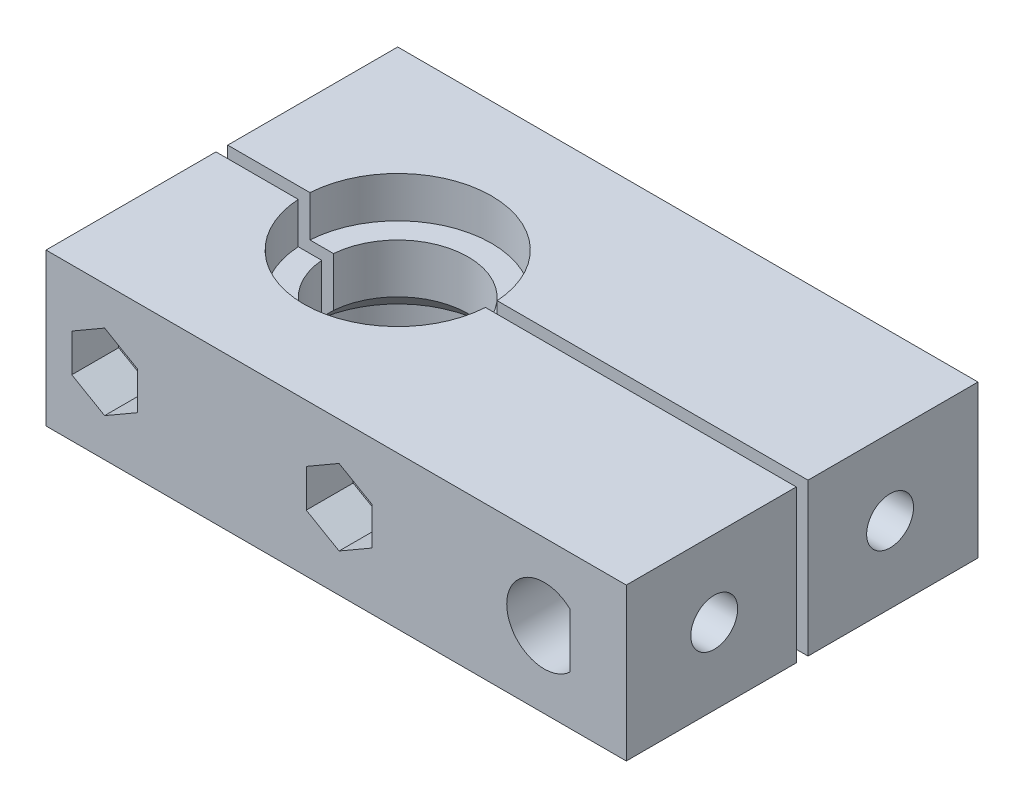
SolidWorks part; units mm, degrees
material "S235JR"
ref_plane "xy" through (0, 0, 0) normal (0, 0, 1) x (1, 0, 0)
ref_plane "xz" through (0, 0, 0) normal (0, 1, 0) x (1, 0, 0)
ref_plane "yz" through (0, 0, 0) normal (1, 0, 0) x (0, 0, -1)
ref_axis "x" through (-88.99, 0, 0) along (1, 0, 0)
ref_axis "y" through (0, 55, 0) along (0, -1, 0)
ref_axis "z" through (0, 0, -88.99) along (0, 0, 1)
sketch "Skizze1" plane through (0, 0, 0) normal (0, 0, 1) x (1, 0, 0)
  line L0 (2, 2.2361) -> (2, -2.2361) construction
  line L1 (-27.5, 6.5) -> (-27.5, -6.5) construction
  line L2 (-42.5, 6.5) -> (7, 6.5)
  line L3 (-42.5, 6.5) -> (-42.5, -6.5)
  line L4 (-42.5, -6.5) -> (7, -6.5)
  line L5 (7, 6.5) -> (7, -6.5)
  line L6 (-37.5, 0) -> (-17.5, 0) construction
  line L7 (2.2, 2.3238) -> (2.2, -2.3238)
  arc A0 (2, 2.2361) -> (2, -2.2361) centre (0, 0) ccw construction
  circle A1 centre (-17.5, 0) radius 1.7
  circle A2 centre (-37.5, 0) radius 1.7
  arc A3 (2.2, 2.3238) -> (2.2, -2.3238) centre (0, 0) ccw
  point P8 (7, 0)
  point P13 (-27.5, 0)
  dimension "D1" = 3
  dimension "D7" = 3.4
  dimension "D2" = 2
  dimension "D3" = 13
  dimension "D4" = 7
  dimension "D5" = 27.5
  dimension "D6" = 15
  dimension "D8" = 20
  dimension "D9" = 0.2
extrude "Aufsatz-Linear austragen1" add sketch "Skizze1" along normal blind 15
sketch "Skizze2" plane through (0, 0, 15) normal (0, 0, 1) x (1, 0, 0)
  line L0 (-35.5, 6.5) -> (-35.5, 3)
  line L1 (-35.5, 3) -> (-33.5, 3)
  line L2 (-33.5, 3) -> (-33.5, -3)
  line L3 (-33.5, -3) -> (-35.5, -3)
  line L4 (-35.5, -3) -> (-35.5, -6.5)
  line L5 (-35.5, -6.5) -> (-27.5, -6.5)
  line L6 (-27.5, -6.5) -> (-27.5, 6.5)
  line L7 (-27.5, 6.5) -> (-35.5, 6.5)
  point P13 (-33.5, 0)
  dimension "D1" = 6
  dimension "D2" = 6
  dimension "D3" = 8
revolve "Schnitt-Rotation1" cut sketch "Skizze2" angle 360 about L6
chamfer "Fase1" distance 1.8 angle 45 1 edges at (-27.5, -3, 9)
sketch "Skizze3" plane through (0, 0, 0) normal (0, 0, 1) x (1, 0, 0)
  line L1 (-14.7, -1.6166) -> (-14.7, 1.6166)
  line L2 (-14.7, 1.6166) -> (-17.5, 3.2332)
  line L3 (-17.5, 3.2332) -> (-20.3, 1.6166)
  line L4 (-20.3, 1.6166) -> (-20.3, -1.6166)
  line L5 (-20.3, -1.6166) -> (-17.5, -3.2332)
  line L6 (-17.5, -3.2332) -> (-14.7, -1.6166)
  line L7 (-37.5, -3.2332) -> (-34.7, -1.6166)
  line L8 (-34.7, -1.6166) -> (-34.7, 1.6166)
  line L9 (-34.7, 1.6166) -> (-37.5, 3.2332)
  line L10 (-37.5, 3.2332) -> (-40.3, 1.6166)
  line L11 (-40.3, 1.6166) -> (-40.3, -1.6166)
  line L12 (-40.3, -1.6166) -> (-37.5, -3.2332)
  circle A0 centre (-17.5, 0) radius 2.8 construction
  circle A1 centre (-37.5, 0) radius 2.8 construction
  dimension "D1" = 5.6
extrude "Schnitt-Linear austragen1" cut sketch "Skizze3" along normal blind 4
sketch "Skizze4" plane through (7, 0, 0) normal (1, 0, 0) x (0, 0, -1)
  line L0 (-15, -6.5) -> (0, 6.5) construction
  circle A0 centre (-7.5, 0) radius 2
  dimension "D1" = 4
extrude "Schnitt-Linear austragen2" cut sketch "Skizze4" against normal up to surface (4.8 mm away) up to face at (2.2, 0, 7.5)
mirror "Spiegeln1" about plane through (0, 0, 15) normal (0, 0, 1) of bodies 104
sketch "Skizze5" plane through (0, 0, 0) normal (0, 1, 0) x (1, 0, 0)
  line L0 (-27.5, -15) -> (-35.5, -15) construction
  line L1 (-48.449, -14.5) -> (7.699, -14.5)
  line L2 (-48.449, -14.5) -> (-48.449, -15.5)
  line L3 (-48.449, -15.5) -> (7.699, -15.5)
  line L4 (7.699, -14.5) -> (7.699, -15.5)
  point P4 (7.699, -15)
  point P7 (-48.449, -15.5)
  dimension "D1" = 1
extrude "Schnitt-Linear austragen3" cut sketch "Skizze5" against normal through all and the other way through all
